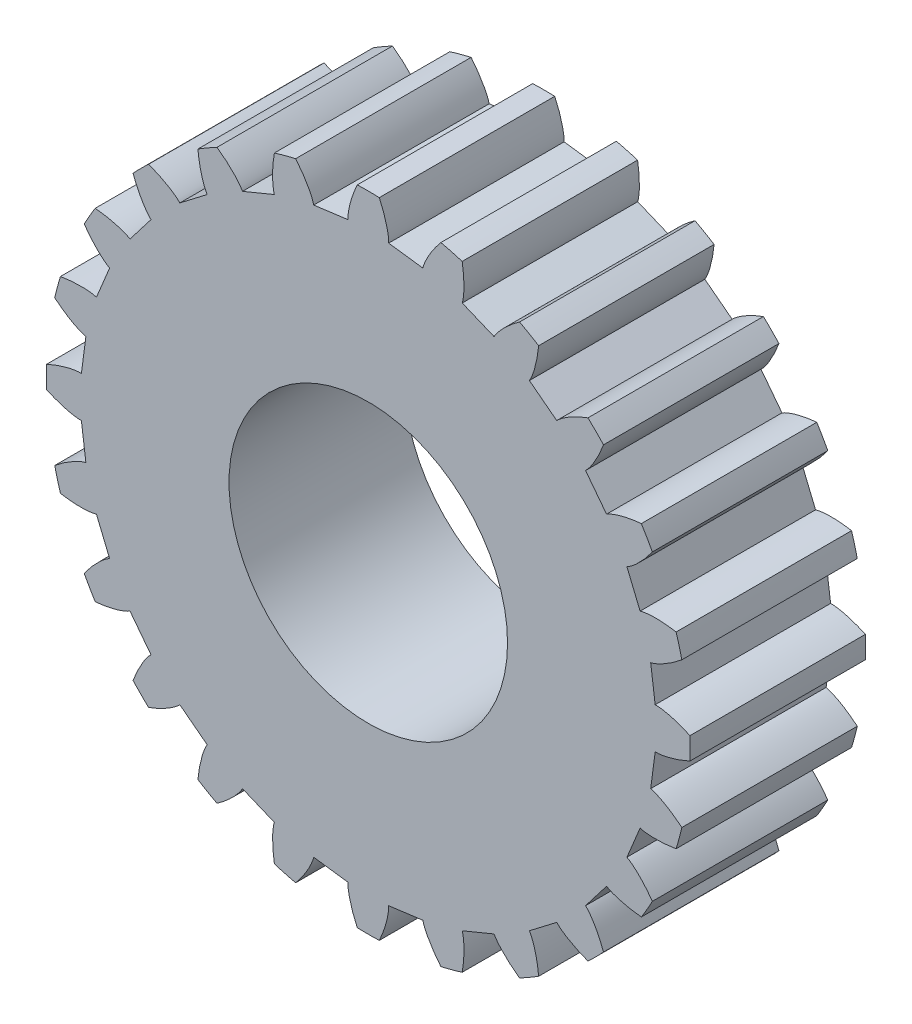
SolidWorks part; units mm, degrees
material "Plain Carbon Steel"
ref_plane "Front Plane" through (0, 0, 0) normal (0, 0, 1) x (1, 0, 0)
ref_plane "Top Plane" through (0, 0, 0) normal (0, 1, 0) x (1, 0, 0)
ref_plane "Right Plane" through (0, 0, 0) normal (1, 0, 0) x (0, 0, -1)
sketch "Sketch1" plane through (0, 0, 0) normal (0, 0, 1) x (1, 0, 0)
  circle A0 centre (0, 0) radius 11.0067
  dimension "D1" = 22.0133
extrude "Boss-Extrude1" add sketch "Sketch1" along normal blind 6
sketch "Sketch2" plane through (0, 0, 0) normal (0, 0, 1) x (1, 0, 0)
  spline S0 degree 4 poles (9.8116, 0.6977) (9.8167, 0.6981) (9.8265, 0.6983) (9.8424, 0.6984) (9.8738, 0.6977) (9.9093, 0.6958) (9.9495, 0.6924) (9.9928, 0.6875) (10.0298, 0.6827) (10.0667, 0.6771) (10.1035, 0.671) (10.1481, 0.6628) (10.2015, 0.652) (10.264, 0.6379) (10.3349, 0.6201) (10.4072, 0.6001) (10.4783, 0.5789) (10.5501, 0.5557) (10.6195, 0.5321) (10.6916, 0.5056) (10.7581, 0.4803) (10.8326, 0.45) (10.8926, 0.4249) (10.9718, 0.3897) (11.0185, 0.3683) (11.0732, 0.3424) (11.0975, 0.3306) (11.1124, 0.3233) knots 0 0 0 0 0 0.015084 0.028532 0.04661 0.092111 0.119476 0.146842 0.174209 0.201575 0.228941 0.256307 0.307035 0.361767 0.4165 0.471232 0.525964 0.580697 0.635429 0.690161 0.744894 0.799626 0.854358 0.909091 0.954545 1 1 1 1 1 construction
  spline S1 degree 4 poles (9.8116, 0.6977) (9.8167, 0.6981) (9.8265, 0.6983) (9.8424, 0.6984) (9.8738, 0.6977) (9.9093, 0.6958) (9.9495, 0.6924) (9.9928, 0.6875) (10.0298, 0.6827) (10.0667, 0.6771) (10.1035, 0.671) (10.1481, 0.6628) (10.2015, 0.652) (10.264, 0.6379) (10.3349, 0.6201) (10.4072, 0.6001) (10.4783, 0.5789) (10.5501, 0.5557) (10.6195, 0.5321) (10.6916, 0.5056) (10.7581, 0.4803) (10.8326, 0.45) (10.8926, 0.4249) (10.9546, 0.3973) (10.9848, 0.3837) (11.0002, 0.3766) knots 0 0 0 0 0 0.015084 0.028532 0.04661 0.092111 0.119476 0.146842 0.174209 0.201575 0.228941 0.256307 0.307035 0.361767 0.4165 0.471232 0.525964 0.580697 0.635429 0.690161 0.744894 0.799626 0.854358 0.909091 0.909091 0.909091 0.909091 0.909091
  spline S2 degree 4 poles (9.6579, 1.8655) (9.6629, 1.8665) (9.6724, 1.8687) (9.6878, 1.8728) (9.7179, 1.8815) (9.7517, 1.8926) (9.7897, 1.9063) (9.8302, 1.9222) (9.8647, 1.9365) (9.8989, 1.9514) (9.9329, 1.9669) (9.9738, 1.9863) (10.0227, 2.0106) (10.0794, 2.0404) (10.1433, 2.0759) (10.2079, 2.1139) (10.2711, 2.1528) (10.3344, 2.1938) (10.3954, 2.2346) (10.4581, 2.2788) (10.5158, 2.3204) (10.5799, 2.369) (10.6315, 2.4088) (10.6988, 2.4633) (10.7384, 2.4961) (10.7845, 2.5352) (10.8049, 2.5529) (10.8174, 2.5638) knots 0 0 0 0 0 0.015084 0.028532 0.04661 0.092111 0.119476 0.146842 0.174209 0.201575 0.228941 0.256307 0.307035 0.361767 0.4165 0.471232 0.525964 0.580697 0.635429 0.690161 0.744894 0.799626 0.854358 0.909091 0.954545 1 1 1 1 1 construction
  spline S3 degree 4 poles (9.6579, 1.8655) (9.6629, 1.8665) (9.6724, 1.8687) (9.6878, 1.8728) (9.7179, 1.8815) (9.7517, 1.8926) (9.7897, 1.9063) (9.8302, 1.9222) (9.8647, 1.9365) (9.8989, 1.9514) (9.9329, 1.9669) (9.9738, 1.9863) (10.0227, 2.0106) (10.0794, 2.0404) (10.1433, 2.0759) (10.2079, 2.1139) (10.2711, 2.1528) (10.3344, 2.1938) (10.3954, 2.2346) (10.4581, 2.2788) (10.5158, 2.3204) (10.5799, 2.369) (10.6315, 2.4088) (10.6842, 2.4515) (10.7098, 2.4725) (10.7229, 2.4833) knots 0 0 0 0 0 0.015084 0.028532 0.04661 0.092111 0.119476 0.146842 0.174209 0.201575 0.228941 0.256307 0.307035 0.361767 0.4165 0.471232 0.525964 0.580697 0.635429 0.690161 0.744894 0.799626 0.854358 0.909091 0.909091 0.909091 0.909091 0.909091
  spline S4 degree 1 poles (9.6579, 1.8655) (9.8116, 0.6977) knots 0 0 1 1 construction
  spline S5 degree 1 poles (9.6579, 1.8655) (9.8116, 0.6977) knots 0 0 1 1
  spline S6 degree 1 poles (11.0002, 0.3766) (59.9649, 2.0528) knots 0 0 1 1 construction
  spline S7 degree 1 poles (11.0002, 0.3766) (59.9649, 2.0528) knots 0 0 1 1
  spline S8 degree 4 poles (59.9936, 0.8853) (59.9922, 0.9686) (59.9893, 1.1297) (59.986, 1.3474) (59.9692, 1.9373) (59.9605, 2.1956) (59.9293, 2.9561) (59.9043, 3.3875) (59.8677, 4.0111) (59.83, 4.5186) (59.7848, 5.0956) (59.736, 5.63) (59.6813, 6.1892) (59.6219, 6.733) (59.5574, 7.2845) (59.4876, 7.8317) (59.4134, 8.3783) (59.333, 8.9277) (59.2496, 9.4683) (59.1577, 10.0226) (59.0665, 10.5515) (58.9608, 11.1205) (58.8659, 11.6205) (58.7399, 12.2323) (58.6523, 12.6554) (58.4856, 13.3982) (58.4273, 13.6499) (58.2908, 14.224) (58.2375, 14.4352) (58.1987, 14.5915) (58.1785, 14.6723) knots 0 0 0 0 0 0.020959 0.041918 0.083333 0.123016 0.162698 0.202381 0.242063 0.281746 0.321429 0.361111 0.400794 0.440476 0.480159 0.519841 0.559524 0.599206 0.638889 0.678571 0.718254 0.757937 0.797619 0.837302 0.876984 0.916667 0.958082 0.979041 1 1 1 1 1 construction
  spline S9 degree 4 poles (59.9649, 2.0528) (59.9609, 2.1679) (59.9524, 2.3919) (59.9293, 2.9561) (59.9043, 3.3875) (59.8677, 4.0111) (59.83, 4.5186) (59.7848, 5.0956) (59.736, 5.63) (59.6813, 6.1892) (59.6219, 6.733) (59.5574, 7.2845) (59.4876, 7.8317) (59.4134, 8.3783) (59.333, 8.9277) (59.2496, 9.4683) (59.1577, 10.0226) (59.0665, 10.5515) (58.9608, 11.1205) (58.8659, 11.6205) (58.7399, 12.2323) (58.6523, 12.6554) (58.5286, 13.2065) (58.4789, 13.425) (58.4529, 13.5372) knots 0.083333 0.083333 0.083333 0.083333 0.083333 0.123016 0.162698 0.202381 0.242063 0.281746 0.321429 0.361111 0.400794 0.440476 0.480159 0.519841 0.559524 0.599206 0.638889 0.678571 0.718254 0.757937 0.797619 0.837302 0.876984 0.916667 0.916667 0.916667 0.916667 0.916667
  spline S10 degree 1 poles (58.4529, 13.5372) (10.7229, 2.4833) knots 0 0 1 1 construction
  spline S11 degree 1 poles (58.4529, 13.5372) (10.7229, 2.4833) knots 0 0 1 1
extrude "Cut-Extrude2" cut sketch "Sketch2" against normal blind 7 and the other way blind 7
ref_axis "Axis1" through (0, 0, -0.3) along (0, 0, 1)
pattern_circular "CirPattern1" count 24 over 360 about axis through (0, 0, -0.3) along (0, 0, 1) of "Cut-Extrude2"
sketch "Sketch3" plane through (0, 0, 0) normal (0, 0, 1) x (1, 0, 0)
  circle A0 centre (0, 0) radius 4.7625
  dimension "D1" = 9.525
extrude "Cut-Extrude4" cut sketch "Sketch3" against normal blind 8 and the other way blind 8
